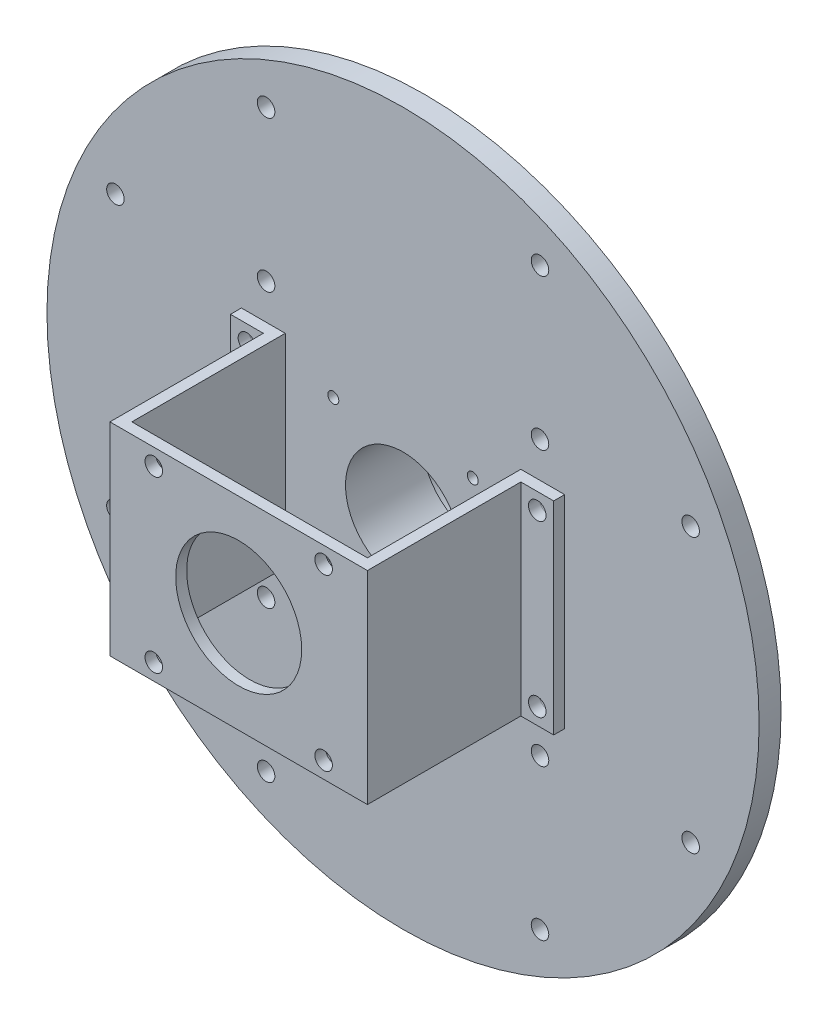
SolidWorks part; units mm, degrees
other "MotorHolder"
other "Disk"
ref_plane "Plan de face" through (0, 0, 0) normal (0, 0, 1) x (1, 0, 0)
ref_plane "Plan de dessus" through (0, 0, 0) normal (0, 1, 0) x (1, 0, 0)
ref_plane "Plan de droite" through (0, 0, 0) normal (1, 0, 0) x (0, 0, -1)
sketch "Esquisse1" plane through (0, 0, 0) normal (0, 0, 1) x (1, 0, 0)
  circle A0 centre (0, 0) radius 65
  dimension "D1" = 130
extrude "Boss.-Extru.1" add sketch "Esquisse1" along normal blind 4
sketch "Esquisse2" plane through (0, 0, 4) normal (0, 0, 1) x (1, 0, 0)
  line L1 (-26.5, 15.5) -> (26.5, 15.5) construction
  line L2 (-26.5, 15.5) -> (-26.5, -15.5) construction
  line L3 (-26.5, -15.5) -> (26.5, -15.5) construction
  line L4 (26.5, 15.5) -> (26.5, -15.5) construction
  circle A0 centre (-26.5, 15.5) radius 1.6
  circle A1 centre (-26.5, -15.5) radius 1.6
  circle A2 centre (26.5, 15.5) radius 1.6
  circle A3 centre (26.5, -15.5) radius 1.6
  point P4 (26.5, 0)
  point P7 (0, 15.5)
  dimension "D3" = 3.2
  dimension "D1" = 31
  dimension "D2" = 53
extrude "Enlèv. mat.-Extru.1" cut sketch "Esquisse2" against normal through all
sketch "Esquisse6" plane through (0, 0, 4) normal (0, 0, 1) x (1, 0, 0)
  circle A0 centre (0, 0) radius 10.5
  dimension "D1" = 21
extrude "Enlèv. mat.-Extru.2" cut sketch "Esquisse6" against normal through all
sketch "Esquisse7" plane through (0, 0, 0) normal (0, 0, -1) x (-1, 0, 0)
  circle A0 centre (0, 0) radius 10.5 construction
  circle A1 centre (0, 0) radius 10.5
  circle A2 centre (0, 0) radius 14
  dimension "D1" = 3.5
extrude "Boss.-Extru.5" add sketch "Esquisse7" along normal blind 10
sketch "Esquisse8" plane through (0, 0, -10) normal (0, 0, -1) x (-1, 0, 0)
  circle A0 centre (0, 0) radius 14 construction
  circle A1 centre (0, 0) radius 14
  circle A2 centre (0, 0) radius 11.1
  dimension "D1" = 22.2
extrude "Boss.-Extru.6" add sketch "Esquisse8" along normal blind 15
sketch "Esquisse10" plane through (0, 0, 0) normal (0, 0, -1) x (-1, 0, 0)
  line L1 (-1.5, 13.9194) -> (1.5, 13.9194)
  line L2 (-1.5, 13.9194) -> (-1.5, 43.9194)
  line L3 (-1.5, 43.9194) -> (1.5, 43.9194)
  line L4 (1.5, 13.9194) -> (1.5, 43.9194)
  circle A0 centre (0, 0) radius 14 construction
  point P7 (0, 13.9194)
  dimension "D1" = 3
  dimension "D2" = 30
extrude "Boss.-Extru.7" add sketch "Esquisse10" along normal up to surface (25 mm away) up to face at (-14, 0, -25)
chamfer "Chanfrein1" distance 24 distance2 30 1 edges at (0, 43.9194, -25) first distance on face at (0, 43.9194, -12.5)
pattern_circular "Répétition circulaire1" count 4 over 360 about axis through (0, 0, 0) along (0, 0, 1) of "Chanfrein1", "Boss.-Extru.7"
chamfer "Chanfrein2" distance 4 angle 45 12 edges at (1.5, 28.9194, 0) (28.9194, 1.5, 0) (9.8995, 9.8995, 0) (28.9194, -1.5, 0) (1.5, -28.9194, 0) (9.8995, -9.8995, 0) (-1.5, -28.9194, 0) (-28.9194, -1.5, 0) (-9.8995, -9.8995, 0) (-28.9194, 1.5, 0) (-1.5, 28.9194, 0) (-9.8995, 9.8995, 0)
sketch "Esquisse11" plane through (0, 0, 4) normal (0, 0, 1) x (1, 0, 0)
  line L1 (-25, 52.5) -> (25, 52.5) construction
  line L2 (-25, 52.5) -> (-25, 25) construction
  line L3 (-25, 25) -> (25, 25) construction
  line L4 (25, 52.5) -> (25, 25) construction
  circle A0 centre (-25, 25) radius 1.6
  circle A1 centre (-25, 52.5) radius 1.6
  circle A2 centre (25, 52.5) radius 1.6
  circle A3 centre (25, 25) radius 1.6
  point P8 (0, 25)
  dimension "D1" = 3.2
  dimension "D2" = 25
  dimension "D3" = 27.5
  dimension "D4" = 50
extrude "Enlèv. mat.-Extru.3" cut sketch "Esquisse11" against normal up to next
pattern_circular "Répétition circulaire2" count 4 over 360 about axis through (0, 0, 0) along (0, 0, 1) of "Enlèv. mat.-Extru.3", "Boss.-Extru.6"
sketch "Esquisse13" plane through (0, 0, 0) normal (0, 0, -1) x (-1, 0, 0)
  circle A0 centre (-12.7279, -12.7279) radius 1
  arc A1 (-17.1391, -5.5) -> (-5.5, -17.1391) centre (0, 0) ccw construction
  dimension "D1" = 2
extrude "Enlèv. mat.-Extru.4" cut sketch "Esquisse13" against normal through all both and the other way through all
pattern_circular "Répétition circulaire3" count 4 over 360 about axis through (0, 0, 0) along (0, 0, 1) of "Enlèv. mat.-Extru.4"
sketch "Esquisse3" plane through (0, 0, 4) normal (0, 0, 1) x (1, 0, 0)
  line L0 (-21.5, 0) -> (21.5, 0) construction
  line L1 (-21.5, -18.5) -> (-29.5, -18.5)
  line L2 (-21.5, -18.5) -> (-21.5, 18.5)
  line L3 (-21.5, 18.5) -> (-29.5, 18.5)
  line L4 (-29.5, -18.5) -> (-29.5, 18.5)
  line L5 (21.5, 18.5) -> (29.5, 18.5)
  line L6 (21.5, 18.5) -> (21.5, -18.5)
  line L7 (21.5, -18.5) -> (29.5, -18.5)
  line L8 (29.5, 18.5) -> (29.5, -18.5)
  circle A0 centre (-26.5, 15.5) radius 1.6 construction
  circle A1 centre (-26.5, -15.5) radius 1.6 construction
  circle A2 centre (26.5, -15.5) radius 1.6 construction
  circle A3 centre (26.5, 15.5) radius 1.6 construction
  circle A4 centre (-26.5, -15.5) radius 1.6
  circle A5 centre (26.5, -15.5) radius 1.6
  circle A6 centre (26.5, 15.5) radius 1.6
  circle A7 centre (-26.5, 15.5) radius 1.6
  dimension "D3" = 3
  dimension "D1" = 5
  dimension "D2" = 3
extrude "Boss.-Extru.2" add sketch "Esquisse3" along normal blind 2 separate body
sketch "Esquisse4" plane through (0, 0, 6) normal (0, 0, 1) x (1, 0, 0)
  line L0 (-29.5, -18.5) -> (-21.5, -18.5) construction
  line L1 (-21.5, 18.5) -> (-23.5, 18.5)
  line L2 (-21.5, 18.5) -> (-21.5, -18.5)
  line L3 (-21.5, -18.5) -> (-23.5, -18.5)
  line L4 (-23.5, 18.5) -> (-23.5, -18.5)
  line L5 (29.5, 18.5) -> (21.5, 18.5) construction
  line L6 (21.5, 18.5) -> (23.5, 18.5)
  line L7 (21.5, 18.5) -> (21.5, -18.5)
  line L8 (21.5, -18.5) -> (23.5, -18.5)
  line L9 (23.5, 18.5) -> (23.5, -18.5)
  line L10 (21.5, 18.5) -> (21.5, -18.5) construction
  line L11 (21.5, -18.5) -> (29.5, -18.5) construction
  dimension "D1" = 2
  dimension "D2" = 2
extrude "Boss.-Extru.3" add sketch "Esquisse4" along normal blind 26
sketch "Esquisse5" plane through (0, 0, 32) normal (0, 0, 1) x (1, 0, 0)
  line L0 (23.5, -18.5) -> (23.5, 18.5) construction
  line L1 (-23.5, -18.5) -> (23.5, -18.5)
  line L2 (-23.5, -18.5) -> (-23.5, 18.5)
  line L3 (-23.5, 18.5) -> (23.5, 18.5)
  line L4 (23.5, -18.5) -> (23.5, 18.5)
  line L6 (-15.5, -15.5) -> (15.5, -15.5) construction
  line L7 (-15.5, -15.5) -> (-15.5, 15.5) construction
  line L8 (-15.5, 15.5) -> (15.5, 15.5) construction
  line L9 (15.5, -15.5) -> (15.5, 15.5) construction
  circle A0 centre (0, 0) radius 11.5
  circle A1 centre (-15.5, 15.5) radius 1.6
  circle A2 centre (-15.5, -15.5) radius 1.6
  circle A3 centre (15.5, -15.5) radius 1.6
  circle A4 centre (15.5, 15.5) radius 1.6
  point P14 (0, -15.5)
  point P15 (-15.5, 0)
  dimension "D1" = 23
  dimension "D3" = 3.2
  dimension "D2" = 31
extrude "Boss.-Extru.4" add sketch "Esquisse5" along normal blind 2
